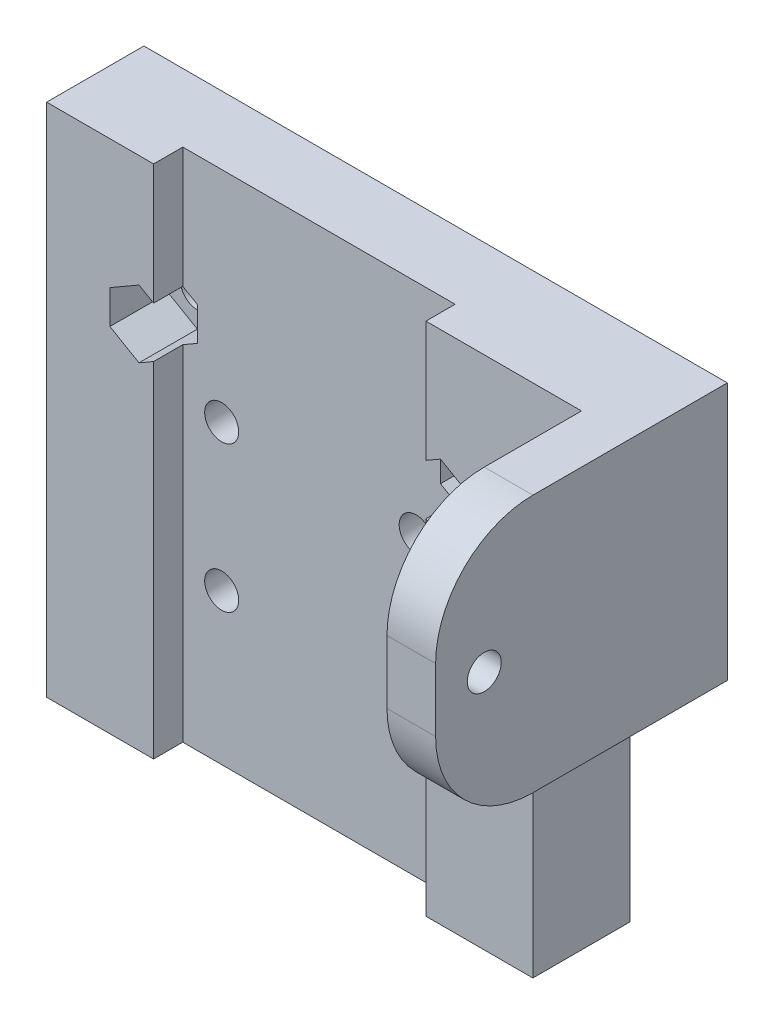
SolidWorks part; units mm, degrees
ref_plane "前视基准面" through (0, 0, 0) normal (0, 0, 1) x (1, 0, 0)
ref_plane "上视基准面" through (0, 0, 0) normal (0, 1, 0) x (1, 0, 0)
ref_plane "右视基准面" through (0, 0, 0) normal (1, 0, 0) x (0, 0, -1)
sketch "草图1" plane through (0, 0, 0) normal (0, 0, 1) x (1, 0, 0)
  line L0 (25, 0) -> (25, -26.5) construction
  line L1 (0, 0) -> (50, 0)
  line L2 (0, 0) -> (0, -53)
  line L3 (0, -53) -> (50, -53)
  line L4 (50, 0) -> (50, -53)
  line L5 (0, -26.5) -> (50, -26.5) construction
  circle A0 centre (35, -22.5) radius 1.75
  circle A1 centre (40.5, -15) radius 1.75
  circle A2 centre (35, -37.5) radius 1.75
  circle A3 centre (15, -37.5) radius 1.75
  circle A4 centre (15, -22.5) radius 1.75
  circle A5 centre (9.5, -15) radius 1.75
  dimension "D3" = 3.5
  dimension "D4" = 20
  dimension "D5" = 15
  dimension "D6" = 7.5
  dimension "D7" = 5.5
  dimension "D8" = 3.5
  dimension "D9" = 3.5
  dimension "D10" = 15.5
  dimension "D11" = 15
  dimension "D1" = 53
  dimension "D2" = 50
extrude "凸台-拉伸1" add sketch "草图1" along normal blind 10
sketch "草图2" plane through (0, 0, 10) normal (0, 0, 1) x (1, 0, 0)
  line L0 (50, 0) -> (0, 0) construction
  line L1 (11, 0) -> (39, 0)
  line L2 (11, 0) -> (11, -53)
  line L3 (11, -53) -> (39, -53)
  line L4 (39, 0) -> (39, -53)
  line L5 (0, -53) -> (50, -53) construction
  line L6 (50, -53) -> (50, 0) construction
  dimension "D1" = 28
  dimension "D2" = 11
extrude "切除-拉伸1" cut sketch "草图2" against normal blind 3
sketch "草图3" plane through (0, 0, 10) normal (0, 0, 1) x (1, 0, 0)
  line L1 (9.5, -18.4641) -> (12.5, -16.7321)
  line L2 (12.5, -16.7321) -> (12.5, -13.2679)
  line L3 (12.5, -13.2679) -> (9.5, -11.5359)
  line L4 (9.5, -11.5359) -> (6.5, -13.2679)
  line L5 (6.5, -13.2679) -> (6.5, -16.7321)
  line L6 (6.5, -16.7321) -> (9.5, -18.4641)
  line L7 (40.5, -18.4641) -> (43.5, -16.7321)
  line L8 (43.5, -16.7321) -> (43.5, -13.2679)
  line L9 (43.5, -13.2679) -> (40.5, -11.5359)
  line L10 (40.5, -11.5359) -> (37.5, -13.2679)
  line L11 (37.5, -13.2679) -> (37.5, -16.7321)
  line L12 (37.5, -16.7321) -> (40.5, -18.4641)
  circle A0 centre (9.5, -15) radius 3 construction
  circle A1 centre (40.5, -15) radius 3 construction
  dimension "D1" = 6
  dimension "D2" = 6
extrude "切除-拉伸2" cut sketch "草图3" against normal blind 6
sketch "草图5" plane through (0, 0, 0) normal (0, 0, -1) x (-1, 0, 0)
  circle A0 centre (-35, -37.5) radius 3
  circle A1 centre (-35, -22.5) radius 3
  circle A2 centre (-15, -37.5) radius 3
  circle A3 centre (-15, -22.5) radius 3
  dimension "D1" = 6
  dimension "D2" = 6
  dimension "D3" = 6
  dimension "D4" = 6
extrude "切除-拉伸4" cut sketch "草图5" against normal blind 3.2
sketch "草图6" plane through (0, 0, 0) normal (0, 0, -1) x (-1, 0, 0)
  line L1 (0, 0) -> (10, 0)
  line L2 (0, 0) -> (0, -26.5)
  line L3 (0, -26.5) -> (10, -26.5)
  line L4 (10, 0) -> (10, -26.5)
  dimension "D1" = 10
  dimension "D2" = 26.5
extrude "凸台-拉伸2" add sketch "草图6" against normal blind 30
sketch "草图7" plane through (0, 0, 30) normal (0, 0, 1) x (1, 0, 0)
  line L0 (-10, 0) -> (0, 0) construction
  line L1 (0, -26.5) -> (-5, -26.5)
  line L2 (0, -26.5) -> (0, 0)
  line L3 (0, 0) -> (-5, 0)
  line L4 (-5, -26.5) -> (-5, 0)
extrude "切除-拉伸5" cut sketch "草图7" against normal blind 20
fillet "圆角2" radius 10 2 edges at (-7.5, 0, 30) (-7.5, -26.5, 30)
fillet "圆角3" radius 10 1 edges at (0, -26.5, 5)
sketch "草图8" plane through (-5, 0, 0) normal (1, 0, 0) x (0, 0, -1)
  line L0 (-10, 0) -> (-10, -26.5) construction
  line L1 (-10, 0) -> (-20, 0) construction
  circle A0 centre (-25, -13.25) radius 1.75
  dimension "D1" = 3.5
  dimension "D2" = 15
  dimension "D3" = 13.25
extrude "切除-拉伸6" cut sketch "草图8" against normal blind 20
mirror "镜向1" about plane through (50, 0, 10) normal (-1, 0, 0) of bodies 113
sketch "草图9" plane through (0, 0, 30) normal (0, 0, 1) x (1, 0, 0)
  line L0 (61, 0) -> (39, 0) construction
  line L1 (50, 0) -> (-20.1887, 0)
  line L2 (50, 0) -> (50, -56.5357)
  line L3 (50, -56.5357) -> (-20.1887, -56.5357)
  line L4 (-20.1887, 0) -> (-20.1887, -56.5357)
extrude "切除-拉伸7" cut sketch "草图9" against normal through all
